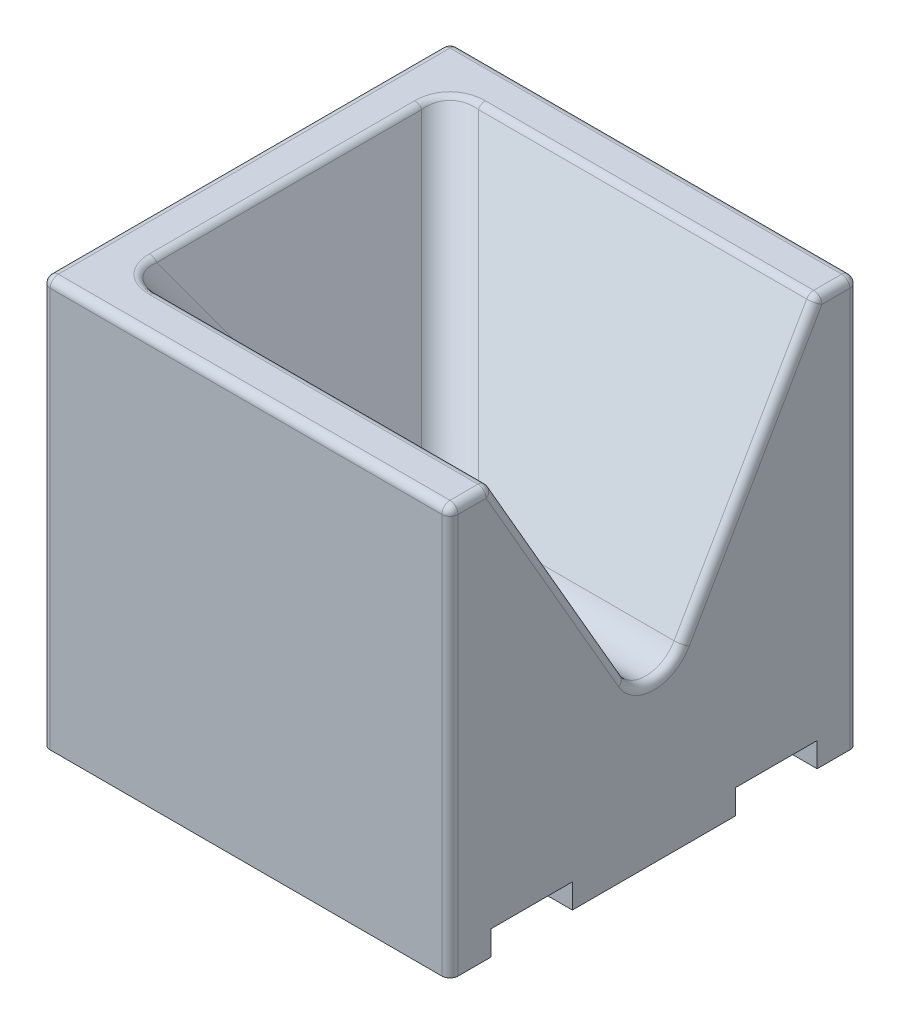
SolidWorks part; units mm, degrees
ref_plane "Front Plane" through (0, 0, 0) normal (0, 0, 1) x (1, 0, 0)
ref_plane "Top Plane" through (0, 0, 0) normal (0, 1, 0) x (1, 0, 0)
ref_plane "Right Plane" through (0, 0, 0) normal (1, 0, 0) x (0, 0, -1)
sketch "Sketch1" plane through (0, 0, 0) normal (0, 1, 0) x (1, 0, 0)
  line L1 (0, -25) -> (50, -25)
  line L2 (0, -25) -> (0, 25)
  line L3 (0, 25) -> (50, 25)
  line L4 (50, -25) -> (50, 25)
  line L5 (0, -25) -> (50, 25) construction
  line L6 (0, 25) -> (50, -25) construction
  point P4 (25, 0)
  point P5 (0, 0)
  dimension "D1" = 50
extrude "Boss-Extrude1" add sketch "Sketch1" along normal blind 50
sketch "Sketch2" plane through (0, 0, 0) normal (1, 0, 0) x (0, 0, -1)
  line L0 (20, 50) -> (0, 15.359)
  line L1 (25, 50) -> (-25, 50) construction
  line L3 (0, 15.359) -> (-20, 50)
  line L4 (-20, 50) -> (20, 50)
  line L5 (25, 50) -> (25, 0) construction
  point P5 (0, 50)
  point P6 (0, 0)
  point P7 (14.8999, 50)
  point P10 (0, 17.9052)
  dimension "D1" = 30
  dimension "D2" = 40
extrude "Cut-Extrude1" cut sketch "Sketch2" along normal blind 50
sketch "Sketch3" plane through (0, 0, 0) normal (0, 0, 1) x (1, 0, 0)
  line L0 (0, 50) -> (5, 50)
  line L1 (0, 50) -> (50, 50) construction
  line L2 (5, 50) -> (33.8675, 0)
  line L3 (0, 0) -> (50, 0) construction
  line L4 (33.8675, 0) -> (0, 0)
  line L5 (0, 0) -> (0, 50)
  dimension "D1" = 5
  dimension "D2" = 30
extrude "Boss-Extrude2" add sketch "Sketch3" along normal blind 25 and the other way blind 25
fillet "Fillet1" radius 4 3 edges at (15, 32.6795, -10) (15, 32.6795, 10) (37.5, 15.359, 0)
sketch "Sketch4" plane through (0, 0, 0) normal (0, 1, 0) x (1, 0, 0)
  line L0 (50, -25) -> (50, 25) construction
  line L1 (50, -20) -> (0, -20)
  line L2 (50, -20) -> (50, -10)
  line L3 (50, -10) -> (0, -10)
  line L4 (0, -20) -> (0, -10)
  line L5 (50, -20) -> (0, -10) construction
  line L6 (50, -10) -> (0, -20) construction
  line L7 (0, 25) -> (0, -25) construction
  point P4 (25, -15)
  point P7 (50, -3.4425)
  dimension "D1" = 10
  dimension "D2" = 10
extrude "Cut-Extrude3" cut sketch "Sketch4" along normal blind 3
sketch "Sketch5" plane through (0, 3, 0) normal (0, -1, 0) x (1, 0, 0)
  line L0 (0, 20) -> (50, 20) construction
  line L1 (6, 20) -> (11, 20)
  line L2 (6, 20) -> (6, 10)
  line L3 (6, 10) -> (11, 10)
  line L4 (11, 20) -> (11, 10)
  line L5 (6, 20) -> (11, 10) construction
  line L6 (6, 10) -> (11, 20) construction
  line L7 (50, 10) -> (0, 10) construction
  line L8 (0, 10) -> (0, 20) construction
  point P4 (8.5, 15)
  dimension "D1" = 5
  dimension "D2" = 6
extrude "Cut-Extrude4" cut sketch "Sketch5" against normal blind 3
pattern_linear "LPattern1" count 4 spacing 11 along (1, 0, 0) of "Cut-Extrude4"
mirror "Mirror1" about plane through (0, 0, 0) normal (0, 0, 1) of "Cut-Extrude4", "Cut-Extrude3", "LPattern1"
fillet "Fillet2" radius 1 17 edges at (50, 35.6795, -11.7321) (50, 19.359, 0) (50, 50, -22.5) (29.2321, 50, -20) (5.9673, 50, -19.0327) (5, 50, 0) (5.9673, 50, 19.0327) (29.2321, 50, 20) (50, 50, 22.5) (25, 50, 25) (0, 50, 0) (25, 50, -25) (0, 25, -25) (0, 25, 25) (50, 25, -25) (50, 35.6795, 11.7321) (50, 25, 25)
